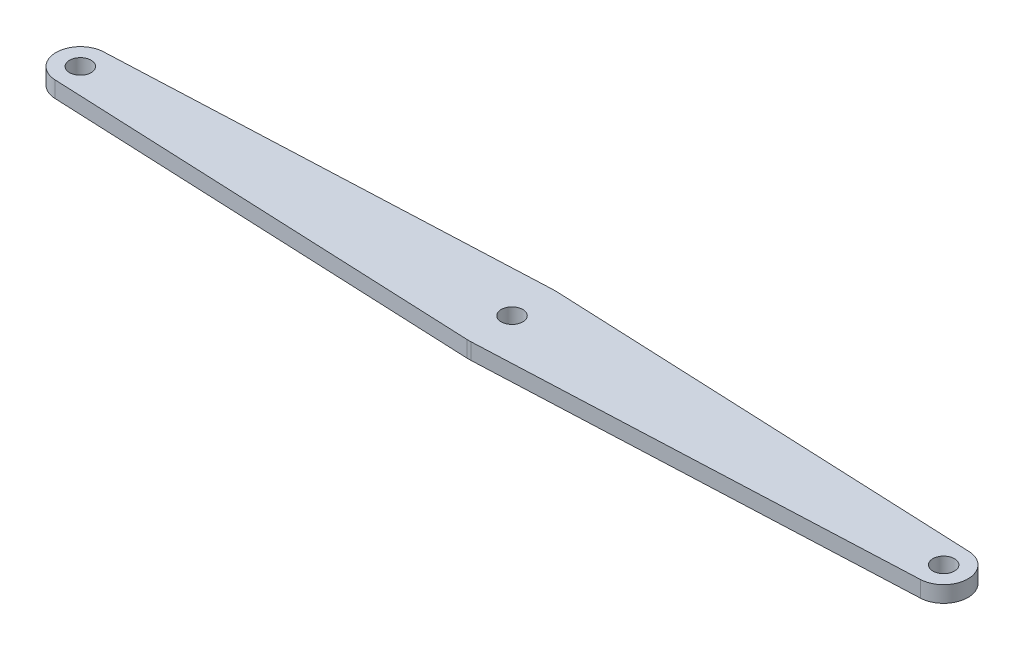
SolidWorks part; units mm, degrees
ref_plane "Спереди" through (0, 0, 0) normal (0, 0, 1) x (1, 0, 0)
ref_plane "Сверху" through (0, 0, 0) normal (0, 1, 0) x (1, 0, 0)
ref_plane "Справа" through (0, 0, 0) normal (1, 0, 0) x (0, 0, -1)
sketch "Эскиз1" plane through (0, 0, 0) normal (0, 1, 0) x (1, 0, 0)
  line L0 (-80, 0) -> (80, 0) construction
  line L1 (-80.1969, 4.4957) -> (-0.35, 7.9923)
  line L2 (-80.1969, -4.4957) -> (-0.35, -7.9923)
  line L3 (0.35, 7.9923) -> (80.1969, 4.4957)
  line L4 (-0.35, -7.9923) -> (0.35, -7.9923)
  line L5 (80.1969, -4.4957) -> (0.35, -7.9923)
  line L6 (-0.35, 7.9923) -> (0.35, 7.9923)
  arc A0 (0.35, 7.9923) -> (-0.35, 7.9923) centre (0, 0) ccw construction
  arc A1 (-80.1969, 4.4957) -> (-80.1969, -4.4957) centre (-80, 0) ccw
  arc A2 (80.1969, -4.4957) -> (80.1969, 4.4957) centre (80, 0) ccw
  arc A3 (-0.35, -7.9923) -> (0.35, -7.9923) centre (0, 0) ccw construction
  point P7 (0, 0)
  dimension "D2" = 8
  dimension "D3" = 4.5
  dimension "D1" = 160
extrude "тело" add sketch "Эскиз1" along normal blind 3
sketch "Эскиз2" plane through (0, 3, 0) normal (0, 1, 0) x (1, 0, 0)
  circle A0 centre (0, 0) radius 2
  dimension "D1" = 4
extrude "отверстие под ось вращения" cut sketch "Эскиз2" against normal through all
sketch "Эскиз3" plane through (0, 3, 0) normal (0, 1, 0) x (1, 0, 0)
  circle A0 centre (-80, 0) radius 2
  circle A1 centre (80, 0) radius 2
  dimension "D1" = 4
extrude "отверстие для крепления тягов" cut sketch "Эскиз3" against normal through all
